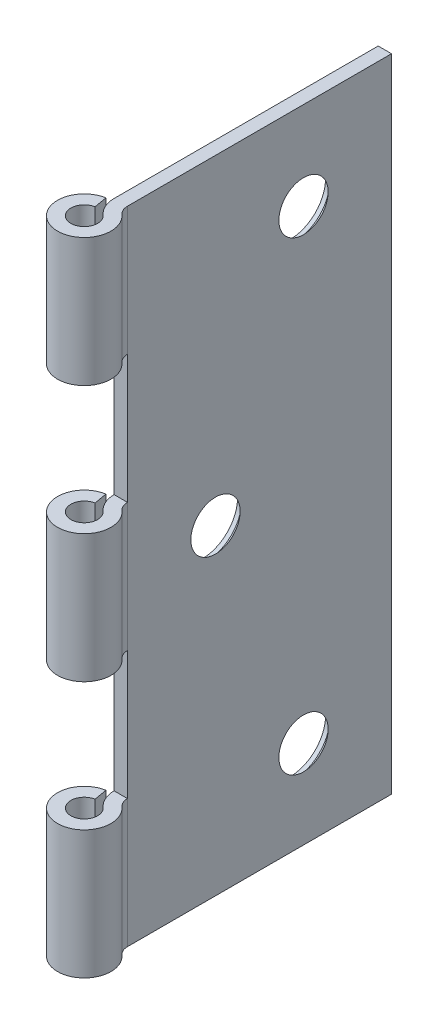
SolidWorks part; units mm, degrees
material "Plain Carbon Steel"
ref_plane "Front Plane" through (0, 0, 0) normal (0, 0, 1) x (1, 0, 0)
ref_plane "Top Plane" through (0, 0, 0) normal (0, 1, 0) x (1, 0, 0)
ref_plane "Right Plane" through (0, 0, 0) normal (1, 0, 0) x (0, 0, -1)
ref_axis "Axis1" through (0, -55, 0) along (0, 1, 0)
sketch "Sketch2" plane through (0, 0, 0) normal (0, 1, 0) x (1, 0, 0)
  line L0 (0, -20.955) -> (0, 20.955) construction
  line L1 (0, 34.925) -> (1.5875, 34.925)
  line L2 (0, 34.925) -> (0, 3.5498)
  line L3 (0, 3.5498) -> (1.5875, 3.5498) construction
  line L4 (1.5875, 34.925) -> (1.5875, 3.5498)
  line L5 (3.175, 0) -> (3.175, 3.5498) construction
  line L6 (-0.5513, 3.1268) -> (0, 0)
  circle A0 centre (0, 0) radius 3.175 construction
  circle A1 centre (0, 0) radius 1.5875 construction
  arc A2 (1.5875, 3.5498) -> (2.1167, 2.3665) centre (3.175, 3.5498) ccw
  arc A3 (0, 3.5498) -> (1.0583, 1.1833) centre (3.175, 3.5498) ccw
  arc A4 (2.1167, 2.3665) -> (-0.5513, 3.1268) centre (0, 0) cw
  circle A5 centre (0, 0) radius 1.5875 construction
  arc A6 (1.0583, 1.1833) -> (-0.2757, 1.5634) centre (0, 0) cw
  point P10 (3.175, 3.5498)
  dimension "D1" = 6.35
  dimension "D2" = 3.175
  dimension "D5" = 31.75
  dimension "D3" = 1.5875
  dimension "D4" = 10
extrude "Boss-Extrude1" add sketch "Sketch2" along normal mid plane 76.2 contours A3 A6 L6 A4 A2 L4 L1 L2 region at (0.5515, 0, -13.0727)
sketch "Sketch3" plane through (0, 0, 0) normal (1, 0, 0) x (0, 0, -1)
  line L0 (3.5498, 38.1) -> (3.5498, -38.1) construction
  line L1 (-3.175, 38.1) -> (-3.175, -38.1) construction
  line L2 (3.5498, 38.1) -> (-3.175, 38.1) construction
  line L3 (3.5498, 38.1) -> (3.5498, 22.86) construction
  line L4 (3.5498, 22.86) -> (-3.175, 22.86) construction
  line L5 (-3.175, 38.1) -> (-3.175, 22.86) construction
  line L7 (3.5498, 22.86) -> (-3.175, 22.86)
  line L8 (3.5498, 22.86) -> (3.5498, 7.62)
  line L9 (3.5498, 7.62) -> (-3.175, 7.62)
  line L10 (-3.175, 22.86) -> (-3.175, 7.62)
  line L11 (3.5498, 7.62) -> (-3.175, 7.62) construction
  line L12 (3.5498, 7.62) -> (3.5498, -7.62) construction
  line L13 (3.5498, -7.62) -> (-3.175, -7.62) construction
  line L14 (-3.175, 7.62) -> (-3.175, -7.62) construction
  line L15 (3.5498, -7.62) -> (-3.175, -7.62)
  line L16 (3.5498, -7.62) -> (3.5498, -22.86)
  line L17 (3.5498, -22.86) -> (-3.175, -22.86)
  line L18 (-3.175, -7.62) -> (-3.175, -22.86)
  line L19 (3.5498, -22.86) -> (-3.175, -22.86) construction
  line L20 (3.5498, -22.86) -> (3.5498, -38.1) construction
  line L21 (3.5498, -38.1) -> (-3.175, -38.1) construction
  line L22 (-3.175, -22.86) -> (-3.175, -38.1) construction
extrude "Cut-Extrude1" cut sketch "Sketch3" against normal through all and the other way through all
hole_wizard "CSK for #8 Flat Head Machine Screw (100)1" positions "Sketch5" profile "Sketch4" countersink size "#8" standard "ANSI Inch" end condition through all
sketch "Sketch5" plane through (0, 0, 0) normal (-1, 0, 0) x (0, 0, 1)
  line L0 (-34.925, 27.6416) -> (-24.4666, 27.6416) construction
  line L1 (-34.925, 38.1) -> (-34.925, -38.1) construction
  line L2 (-24.4666, 27.6416) -> (-24.4666, 0) construction
  line L3 (-24.4666, 0) -> (-14.0082, 0) construction
  line L4 (-14.0082, 0) -> (-14.0082, 7.62) construction
  line L5 (-14.0082, 7.62) -> (-3.5498, 7.62) construction
  line L6 (-3.5498, 22.86) -> (-3.5498, 7.62) construction
  line L9 (-24.4666, 0) -> (-24.4666, -27.6416) construction
  line L11 (-24.4666, 27.6416) -> (-24.4666, 38.1) construction
  line L12 (-34.925, 38.1) -> (-3.5498, 38.1) construction
  point P0 (-24.4666, -27.6416)
  point P2 (-14.0082, 0)
  point P4 (-24.4666, 27.6416)
sketch "Sketch4" plane through (0, -27.6416, -24.4666) normal (0, 1, 0) x (0, 0, 1)
  line L0 (0, 0) -> (0, 3.175)
  line L1 (0, 3.175) -> (2.2479, 3.175)
  line L2 (2.2479, 3.175) -> (2.2479, 2.1598)
  line L3 (2.2479, 2.1598) -> (4.2164, 0.508)
  line L4 (4.2164, 0.508) -> (4.2164, 0)
  line L6 (4.2164, 0) -> (0, 0)
  line L7 (-2.2479, 2.1598) -> (-4.2164, 0.508) construction
  line L11 (0, -6.35) -> (0, 107.95) construction
  dimension "Thru Hole Dia." = 4.4958
  dimension "Thru Hole Depth" = 3.175
  dimension "C'Sink Dia." = 8.4328
  dimension "C'Sink Angle" = 100
  dimension "Head Clearance" = 0.508
